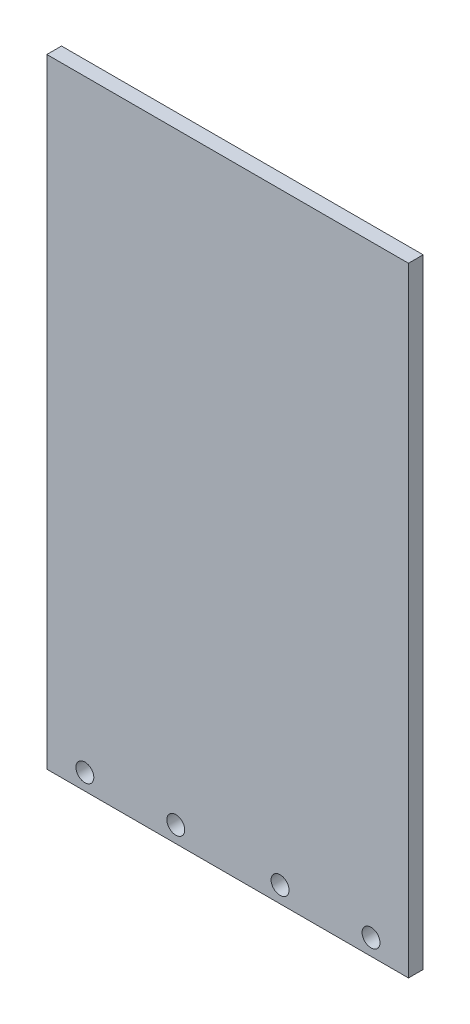
SolidWorks part; units mm, degrees
material "Perspex (TM) GS Acrylic Cast Sheet"
ref_plane "Front Plane" through (0, 0, 0) normal (0, 0, 1) x (1, 0, 0)
ref_plane "Top Plane" through (0, 0, 0) normal (0, 1, 0) x (1, 0, 0)
ref_plane "Right Plane" through (0, 0, 0) normal (1, 0, 0) x (0, 0, -1)
sketch "Sketch1" plane through (0, 0, 0) normal (0, 0, 1) x (1, 0, 0)
  line L1 (-111, -190) -> (111, -190)
  line L2 (-111, -190) -> (-111, 190)
  line L3 (-111, 190) -> (111, 190)
  line L4 (111, -190) -> (111, 190)
  line L5 (-111, -190) -> (111, 190) construction
  line L6 (-111, 190) -> (111, -190) construction
  point P0 (0, 0)
  dimension "D1" = 222
  dimension "D2" = 380
extrude "Boss-Extrude1" add sketch "Sketch1" along normal blind 9
sketch "Sketch2" [suppressed] plane through (0, 0, 9) normal (0, 0, 1) x (1, 0, 0)
  line L0 (87.5, -185) -> (87.5, 185) construction
  line L1 (-87.5, -185) -> (87.5, -185) construction
  circle A0 centre (36.5, -179) radius 3
  dimension "D1" = 6
  dimension "D2" = 48
  dimension "D3" = 6
extrude "Cut-Extrude1" [suppressed] cut sketch "Sketch2" against normal through all
sketch "Sketch4" plane through (0, 0, 0) normal (0, 0, -1) x (-1, 0, 0)
  circle A0 centre (-32.16, -180) radius 5.5
  circle A1 centre (-88, -180) radius 5.5
  circle A2 centre (31.84, -180) radius 5.5
  circle A3 centre (87.68, -180) radius 5.5
  dimension "D1" = 11
extrude "Cut-Extrude2" cut sketch "Sketch4" against normal through all
equation "\"PCLength\"= 145mm'Length across I/O from PS to GPU"
equation "\"PCWidth\"= 340mm'Distance of longest part parallel to GPU(ussually GPU)"
equation "\"PCHeight\"= 180mm'Tallest point with mobo laying flat"
equation "\"WallThickness\"= 9mm'Thickness of each outer tank wall"
equation "\"ThermoBarrierThickness\"= 6mm'Thickness of barrier between hot side and cold side"
equation "\"HotSideGap\"= 36mm'Space in the hot side for a pump"
equation "\"PCClearance\"= 40mm'Clearance from top of tank to top of PC"
equation "\"RadiatorHeight\"= 277.37mm'Final Height from ground of radiators"
equation "\"D1@Sketch1\"=\"PCHeight\" + \"ThermoBarrierThickness\" + \"HotSideGap\""
equation "\"D2@Sketch1\"=\"PCWidth\" + \"PCClearance\""
equation "\"D1@Boss-Extrude1\"=\"WallThickness\""
equation "\"D2@Sketch2\"=\"HotSideGap\" + \"ThermoBarrierThickness\" + 6"
